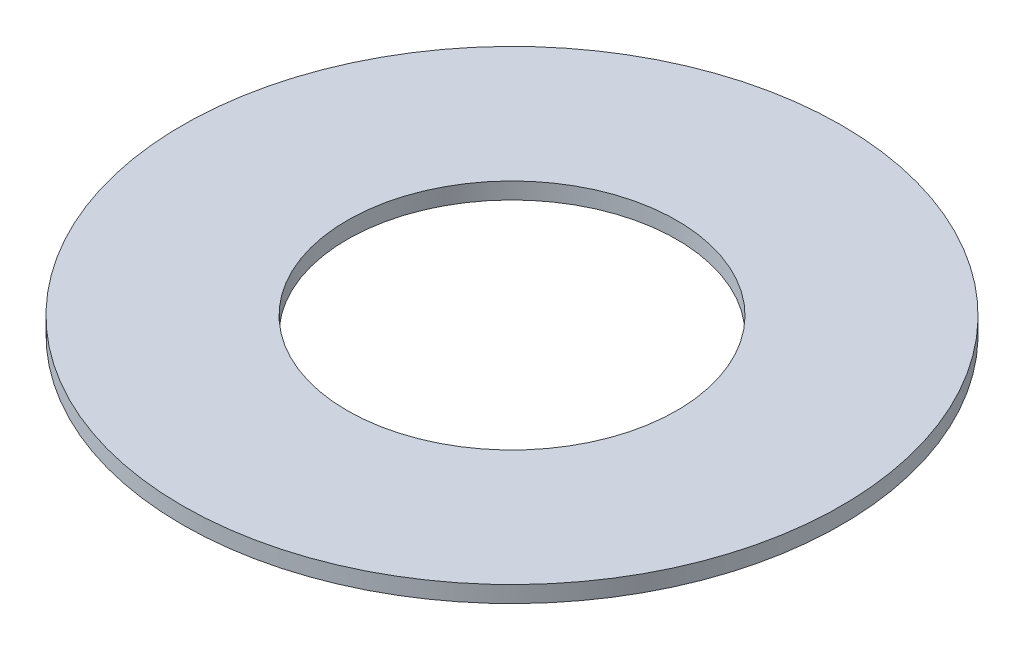
SolidWorks part; units mm, degrees
material "Thornel Mat VMA"
ref_plane "Front Plane" through (0, 0, 0) normal (0, 0, 1) x (1, 0, 0)
ref_plane "Top Plane" through (0, 0, 0) normal (0, 1, 0) x (1, 0, 0)
ref_plane "Right Plane" through (0, 0, 0) normal (1, 0, 0) x (0, 0, -1)
sketch "Sketch1" plane through (0, 0, 0) normal (0, 1, 0) x (1, 0, 0)
  circle A0 centre (0, 0) radius 50
  circle A1 centre (0, 0) radius 100
  dimension "D1" = 100
  dimension "D2" = 200
extrude "Boss-Extrude1" add sketch "Sketch1" along normal mid plane 5
equation "\"lift_fan_diameter\"=100"
equation "\"D1@Sketch1\"=\"lift_fan_diameter\""
equation "\"outer_diameter\"=200"
equation "\"D2@Sketch1\"=\"outer_diameter\""
